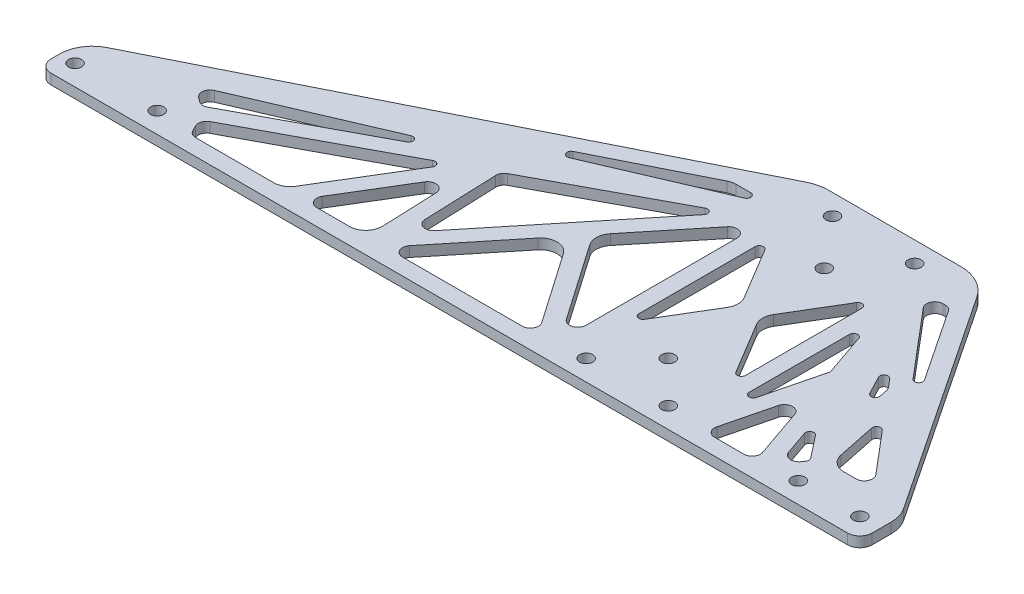
SolidWorks part; units mm, degrees
ref_plane "Front Plane" through (0, 0, 0) normal (0, 0, 1) x (1, 0, 0)
ref_plane "Top Plane" through (0, 0, 0) normal (0, 1, 0) x (1, 0, 0)
ref_plane "Right Plane" through (0, 0, 0) normal (1, 0, 0) x (0, 0, -1)
sketch "Sketch1" plane through (0, 0, 0) normal (0, 1, 0) x (1, 0, 0)
  line L0 (0, 0) -> (254, 0)
  line L2 (203.2, 88.9) -> (152.4, 88.9)
  line L4 (0, 0) -> (0, 12.7)
  line L5 (0, 12.7) -> (152.4, 88.9)
  line L6 (203.2, 88.9) -> (254, 12.7)
  line L7 (254, 12.7) -> (254, 0)
  line L8 (0, 6.35) -> (41.2306, 6.35) construction
  line L9 (254, 6.35) -> (220.1675, 6.35) construction
  line L10 (139.7, 82.55) -> (207.4333, 82.55) construction
  line L11 (156.6333, 76.2) -> (38.0113, 12.7) construction
  line L12 (38.0113, 12.7) -> (22.7185, 24.0592)
  line L13 (226.5259, 15.8112) -> (251.9259, 15.8112)
  line L20 (127, 76.2) -> (211.6667, 76.2)
  line L21 (226.5259, 15.8112) -> (215.9, 0)
  line L22 (38.0113, 12.7) -> (44.45, 0)
  line L23 (156.6333, 76.2) -> (27.2885, 20.6647) construction
  line L24 (156.6333, 76.2) -> (98.8302, 5.08) construction
  line L28 (194.7333, 76.2) -> (226.5259, 15.8112) construction
  line L31 (5.08, 9.5604) -> (153.5992, 83.82)
  line L32 (200.4813, 83.82) -> (153.5992, 83.82)
  line L33 (200.4813, 83.82) -> (248.92, 11.1619)
  line L34 (248.92, 11.1619) -> (248.92, 5.08)
  line L35 (5.08, 5.08) -> (248.92, 5.08)
  line L36 (5.08, 5.08) -> (5.08, 9.5604)
  line L37 (219.314, 5.08) -> (194.7333, 76.2) construction
  line L39 (194.7333, 76.2) -> (245.8205, 15.8112) construction
  line L40 (98.8302, 5.08) -> (97.3223, 44.45) construction
  line L41 (127.7318, 40.64) -> (152.3892, 5.08) construction
  line L42 (207.0237, 40.64) -> (198.1092, 5.08) construction
  line L83 (226.5259, 15.8112) -> (220.2769, 46.0056) construction
  line L84 (207.0237, 40.64) -> (226.5259, 15.8112) construction
  line L107 (97.3223, 44.45) -> (73.4302, 5.08) construction
  line L108 (156.6333, 76.2) -> (194.7333, 12.7) construction
  line L113 (194.7333, 76.2) -> (156.6333, 12.7) construction
  line L114 (155.6312, 78.534) -> (26.2864, 22.9986)
  line L115 (155.4346, 78.4393) -> (36.8125, 14.9393)
  line L116 (154.6622, 77.802) -> (101.1104, 11.9127)
  line L117 (156.6333, 12.7) -> (154.0933, 8.1397)
  line L118 (156.6333, 12.7) -> (194.7333, 12.7)
  line L119 (194.7333, 12.7) -> (200.3598, 0)
  line L120 (153.0965, 6.35) -> (197.5465, 6.35) construction
  line L123 (101.1104, 11.9127) -> (99.5369, 52.9951)
  line L124 (99.5369, 52.9951) -> (96.1931, 47.4852)
  line L125 (125.6445, 39.1927) -> (150.3019, 3.6327)
  line L126 (192.5553, 77.5068) -> (154.4553, 14.0068)
  line L127 (154.4553, 74.8932) -> (192.5553, 11.3932)
  line L128 (156.6333, 12.7) -> (156.6333, 76.2) construction
  line L129 (194.7333, 12.7) -> (194.7333, 76.2) construction
  line L130 (197.2733, 12.7) -> (197.2733, 76.2)
  line L131 (159.1733, 12.7) -> (159.1733, 76.2)
  line L132 (192.1933, 12.7) -> (192.1933, 76.2)
  line L133 (154.0933, 12.7) -> (154.0933, 76.2)
  line L134 (205.8201, 46.2844) -> (228.5234, 17.3801)
  line L137 (205.8201, 46.2844) -> (195.6454, 5.6976)
  line L138 (221.7147, 5.9097) -> (197.134, 77.0297)
  line L139 (192.4858, 75.0167) -> (224.2783, 14.6279)
  line L140 (229.0132, 16.3259) -> (222.7642, 46.5203)
  line L141 (157.6354, 73.866) -> (28.2906, 18.3307)
  line L142 (157.8321, 73.9607) -> (39.21, 10.4607)
  line L143 (158.6044, 74.598) -> (96.5501, -1.7527)
  line L144 (96.5501, -1.7527) -> (95.1077, 35.9049)
  line L145 (95.1077, 35.9049) -> (75.6017, 3.7622)
  line L146 (129.8191, 42.0873) -> (154.4765, 6.5273)
  line L147 (196.9114, 74.8932) -> (158.8114, 11.3932)
  line L148 (158.8114, 77.5068) -> (196.9114, 14.0068)
  line L149 (208.2273, 34.9956) -> (224.5284, 14.2422)
  line L150 (208.2273, 34.9956) -> (200.5729, 4.4624)
  line L151 (216.9134, 4.2503) -> (192.3327, 75.3703)
  line L152 (196.9809, 77.3833) -> (228.7734, 16.9944)
  line L153 (224.0386, 15.2964) -> (217.7896, 45.4908)
  line L154 (71.2588, 6.3978) -> (70.4591, 5.08)
  line L155 (36.8125, 14.9393) -> (35.7571, 14.3744)
  line L156 (39.21, 10.4607) -> (39.1601, 10.434)
  line L157 (154.0933, 12.7) -> (154.0933, 7.0799)
  line L158 (197.2733, 12.7) -> (197.2733, 6.9667)
  line L159 (224.5284, 14.2422) -> (225.0366, 13.5952)
  line L160 (229.0132, 16.3259) -> (229.1197, 15.8112)
  line L161 (192.7942, 74.5595) -> (243.8813, 14.1707)
  line L162 (196.6725, 77.8405) -> (247.7597, 17.4517)
  line L163 (153.766, 7.552) -> (149.5598, 0)
  line L164 (95.5112, 46.3615) -> (71.2588, 6.3978)
  line L165 (99.5369, 52.9951) -> (71.2588, 6.3978) construction
  line L166 (175.6833, 19.05) -> (162.9833, 6.35) construction
  line L167 (175.6833, 19.05) -> (188.3833, 6.35) construction
  line L168 (162.9833, 82.55) -> (175.6833, 67.31) construction
  line L169 (175.6833, 67.31) -> (188.3833, 82.55) construction
  circle A0 centre (4.8683, 6.35) radius 2.032
  circle A1 centre (30.2683, 6.35) radius 2.032
  circle A2 centre (228.6, 6.35) radius 2.032
  circle A3 centre (247.65, 6.35) radius 2.032
  circle A4 centre (162.9833, 82.55) radius 2.032
  circle A5 centre (188.3833, 82.55) radius 2.032
  circle A28 centre (162.9833, 6.35) radius 2.032
  circle A29 centre (188.3833, 6.35) radius 2.032
  arc A32 (197.2733, 12.7) -> (192.1933, 12.7) centre (194.7333, 12.7) cw
  arc A33 (197.2733, 76.2) -> (192.1933, 76.2) centre (194.7333, 76.2) ccw
  arc A34 (159.1733, 12.7) -> (154.0933, 12.7) centre (156.6333, 12.7) cw
  arc A35 (159.1733, 76.2) -> (154.0933, 76.2) centre (156.6333, 76.2) ccw
  arc A37 (155.6312, 78.534) -> (157.6354, 73.866) centre (156.6333, 76.2) cw
  arc A38 (26.2864, 22.9986) -> (28.2906, 18.3307) centre (27.2885, 20.6647) ccw
  arc A39 (155.4346, 78.4393) -> (157.8321, 73.9607) centre (156.6333, 76.2) cw
  arc A40 (36.8125, 14.9393) -> (39.21, 10.4607) centre (38.0113, 12.7) ccw
  arc A41 (154.6622, 77.802) -> (158.6044, 74.598) centre (156.6333, 76.2) cw
  arc A42 (71.2588, 6.3978) -> (75.6017, 3.7622) centre (73.4302, 5.08) ccw
  arc A43 (125.6445, 39.1927) -> (129.8191, 42.0873) centre (127.7318, 40.64) cw
  arc A44 (150.3019, 3.6327) -> (154.4765, 6.5273) centre (152.3892, 5.08) ccw
  arc A45 (192.5553, 77.5068) -> (196.9114, 74.8932) centre (194.7333, 76.2) cw
  arc A46 (154.4553, 14.0068) -> (158.8114, 11.3932) centre (156.6333, 12.7) ccw
  arc A47 (154.4553, 74.8932) -> (158.8114, 77.5068) centre (156.6333, 76.2) cw
  arc A48 (192.5553, 11.3932) -> (196.9114, 14.0068) centre (194.7333, 12.7) ccw
  arc A49 (228.5234, 17.3801) -> (224.5284, 14.2422) centre (226.5259, 15.8112) cw
  arc A50 (195.6454, 5.6976) -> (200.5729, 4.4624) centre (198.1092, 5.08) ccw
  arc A51 (221.7147, 5.9097) -> (216.9134, 4.2503) centre (219.314, 5.08) cw
  arc A52 (197.134, 77.0297) -> (192.3327, 75.3703) centre (194.7333, 76.2) ccw
  arc A53 (192.4858, 75.0167) -> (196.9809, 77.3833) centre (194.7333, 76.2) cw
  arc A54 (224.2783, 14.6279) -> (228.7734, 16.9944) centre (226.5259, 15.8112) ccw
  arc A55 (229.0132, 16.3259) -> (224.0386, 15.2964) centre (226.5259, 15.8112) cw
  arc A56 (222.7642, 46.5203) -> (217.7896, 45.4908) centre (220.2769, 46.0056) ccw
  arc A57 (192.7942, 74.5595) -> (196.6725, 77.8405) centre (194.7333, 76.2) cw
  arc A58 (243.8813, 14.1707) -> (247.7597, 17.4517) centre (245.8205, 15.8112) ccw
  circle A59 centre (175.6833, 19.05) radius 2.032
  circle A60 centre (175.6833, 67.31) radius 2.032
  dimension "D7" = 4.064
  dimension "D8" = 25.4
  dimension "D9" = 132.715
  dimension "D10" = 19.05
  dimension "D11" = 6.35
  dimension "D13" = 19.05
  dimension "D1" = 254
  dimension "D2" = 50.8
  dimension "D3" = 88.9
  dimension "D4" = 152.4
  dimension "D5" = 12.7
  dimension "D6" = 6.35
  dimension "D12" = 25.4
  dimension "D14" = 44.45
  dimension "D15" = 19.05
  dimension "D16" = 25.4
  dimension "D18" = 12.7
  dimension "D19" = 38.1
  dimension "D20" = 19.05
  dimension "D21" = 12.7
  dimension "D22" = 25.4
  dimension "D23" = 50.8
  dimension "D24" = 25.4
  dimension "D29" = 6.35
  dimension "D30" = 38.1
  dimension "D31" = 25.4
  dimension "D32" = 6.35
  dimension "D33" = 2.54
  dimension "D34" = 50.8
  dimension "D35" = 7.552
  dimension "D36" = 12.7
  dimension "D38" = 15.24
  dimension "D17" = 5.08
  dimension "D25" = 2.54
  dimension "D26" = 2.54
  dimension "D27" = 2.54
  dimension "D28" = 2.54
  dimension "D37" = 2.54
extrude "Boss-Extrude1" add sketch "Sketch1" along normal blind 3.175 contours L0 L7 L6 L2 L5 L4 | A0 | A1 | A5 | A4 | A2 | A3
extrude "Cut-Extrude2" cut sketch "Sketch1<3>" along normal through all contours L142 L156 L22 L35 L154 L124 | L155 L115 L124 L141 L12 | L144 L145 L35 | L116 L142 L123 | L125 L143 L35 | L157 L133 L143 L146 L117 | L114 L20 L31 | L130 L158 L137 L151 | L35 L151 L150 | L161 L152 L153 | L161 L140 L160 L13 | L159 L149 L138 L21 | L20 L162 L33 | L131 L126 L127 | L147 L148 L132 | L115 L141 L123 | A28 | A29 | A59 | A60 region at (64.7257, 0, -16.4796) region at (89.2658, 0, -15.355) region at (126.3241, 0, -15.5249) region at (118.3245, 0, -64.21) region at (56.1323, 0, -27.8913) region at (146.3644, 0, -38.8822) region at (115.9087, 0, -40.9571) region at (100.9162, 0, -49.3843) region at (212.3574, 0, -62.2554) region at (208.2553, 0, -13.9673) region at (220.1621, 0, -16.1676) region at (199.6409, 0, -37.9304) region at (163.6893, 0, -44.45) region at (232.1338, 0, -22.7875) region at (215.3763, 0, -44.8583) region at (187.6774, 0, -44.45)
sketch "Sketch1<3>" plane through (0, 0, 0) normal (0, 1, 0) x (1, 0, 0) same geometry as "Sketch1"
fillet "Fillet1" radius 3.81 2 edges at (254, 1.5875, 0) (0, 1.5875, 0)
fillet "Fillet2" radius 10.16 2 edges at (254, 1.5875, -12.7) (0, 1.5875, -12.7)
fillet "Fillet3" radius 12.7 2 edges at (203.2, 1.5875, -88.9) (152.4, 1.5875, -88.9)
fillet "Fillet4" radius 1.27 17 edges at (214.3608, 1.5875, -27.1869) (233.4505, 1.5875, -34.3662) (207.8157, 1.5875, -56.8029) (220.3926, 1.5875, -32.9136) (197.2733, 1.5875, -61.0753) (197.2733, 1.5875, -12.1914) (159.1733, 1.5875, -67.0298) (192.1933, 1.5875, -67.0298) (192.1933, 1.5875, -21.8702) (159.1733, 1.5875, -21.8702) (146.6944, 1.5875, -67.9985) (66.4191, 1.5875, -40.2299) (150.1953, 1.5875, -76.2) (224.7883, 1.5875, -36.74) (103.3533, 1.5875, -50.5595) (90.3319, 1.5875, -37.8269) (225.0366, 1.5875, -13.5952)
fillet "Fillet5" radius 2.54 20 edges at (39.1601, 1.5875, -10.434) (41.8745, 1.5875, -5.08) (99.9212, 1.5875, -42.9602) (101.1104, 1.5875, -11.9127) (95.1077, 1.5875, -35.9049) (76.4014, 1.5875, -5.08) (35.7571, 1.5875, -14.3744) (29.6468, 1.5875, -18.913) (198.0603, 1.5875, -76.2) (205.5613, 1.5875, -76.2) (217.9205, 1.5875, -44.8583) (242.4935, 1.5875, -15.8112) (221.0887, 1.5875, -7.7208) (216.6266, 1.5875, -5.08) (200.7278, 1.5875, -5.08) (207.4116, 1.5875, -31.7419) (154.0933, 1.5875, -69.0476) (149.2983, 1.5875, -5.08) (102.1034, 1.5875, -5.08) (154.0933, 1.5875, -7.0799)
fillet "Fillet6" radius 5.08 8 edges at (229.1197, 1.5875, -15.8112) (96.2884, 1.5875, -5.08) (172.7212, 1.5875, -44.45) (178.6455, 1.5875, -44.45) (130.9066, 1.5875, -40.519) (127.5708, 1.5875, -36.4147) (138.3592, 1.5875, -76.2) (70.4591, 1.5875, -5.08)
